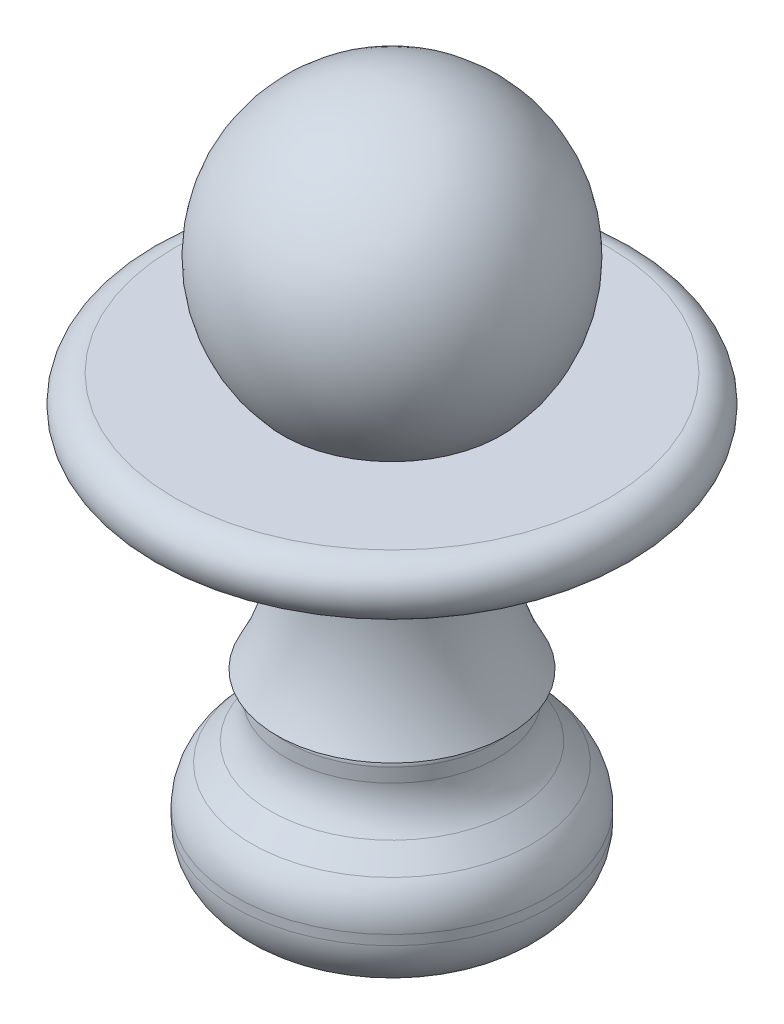
SolidWorks part; units mm, degrees
ref_plane "Front Plane" through (0, 0, 0) normal (0, 0, 1) x (1, 0, 0)
ref_plane "Top Plane" through (0, 0, 0) normal (0, 1, 0) x (1, 0, 0)
ref_plane "Right Plane" through (0, 0, 0) normal (1, 0, 0) x (0, 0, -1)
sketch "Sketch1" plane through (0, 0, 0) normal (0, 0, 1) x (1, 0, 0)
  line L0 (-18.35, 20.3838) -> (-18.35, 21.523)
  line L1 (-16.4901, 26.0131) -> (-14.2712, 28.232)
  line L2 (-12.4114, 32.7221) -> (-12.4114, 34.3502)
  line L3 (-11.1927, 35.5689) -> (-13.5459, 35.5689)
  line L4 (-12.7975, 59.3467) -> (-25.4975, 59.3467)
  line L5 (-25.4975, 65.6967) -> (-12.7975, 65.6967)
  line L13 (0, -5.7615) -> (0, 109.2311) construction
  line L14 (-12, 14.0338) -> (0, 14.0338)
  line L15 (0, 95.0314) -> (0, 14.0338)
  arc A0 (-13.5459, 35.5689) -> (-12.7975, 59.3467) centre (-35.6033, 48.1639) ccw
  arc A1 (-25.4975, 59.3467) -> (-25.4975, 65.6967) centre (-25.4975, 62.5217) cw
  arc A8 (-18.35, 21.523) -> (-16.4901, 26.0131) centre (-12, 21.523) cw
  arc A9 (-14.2712, 28.232) -> (-12.4114, 32.7221) centre (-18.7614, 32.7221) ccw
  arc A10 (-18.35, 20.3838) -> (-12, 14.0338) centre (-12, 20.3838) ccw
  arc A12 (-12.4114, 34.3502) -> (-11.1927, 35.5689) centre (-11.1927, 34.3502) cw
  arc A13 (-12.7975, 65.6967) -> (0, 95.0314) centre (0, 77.5726) cw
  point P13 (0, 0)
  point P15 (0, 0)
  dimension "D1" = 12
  dimension "D3" = 25.4
  dimension "D5" = 12.7
  dimension "D7" = 12.7
  dimension "D9" = 6.35
revolve "Revolve1" add sketch "Sketch1" angle 360 about L13
chamfer "Chamfer1" distance 5 angle 45 1 edges at (0, 59.3467, -12.7975) first distance on face at (0, 59.3467, -12.7975)
sketch "Sketch2" plane through (0, 14.0338, 0) normal (0, -1, 0) x (1, 0, 0)
  circle A0 centre (0, 0) radius 10
  dimension "D1" = 20
extrude "Boss-Extrude1" add sketch "Sketch2" against normal blind 2.54 from offset 0.4 offset against normal yes
